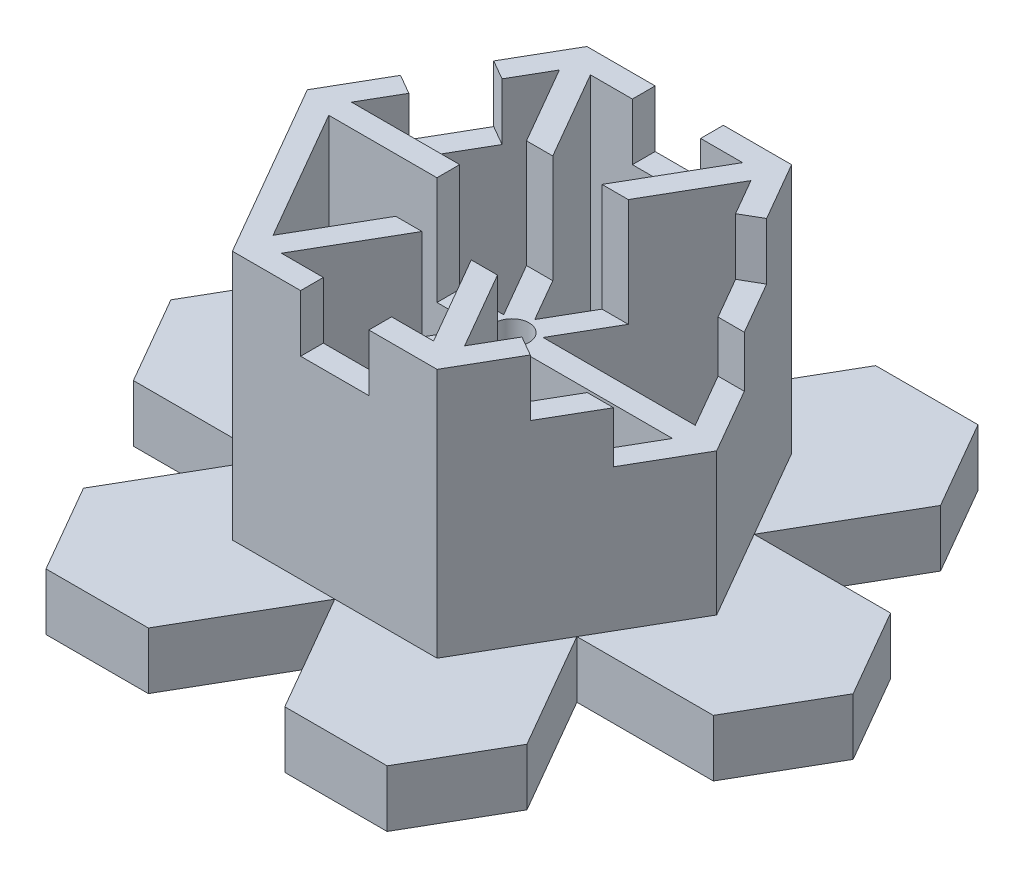
SolidWorks part; units mm, degrees
ref_plane "Alzado" through (0, 0, 0) normal (0, 0, 1) x (1, 0, 0)
ref_plane "Planta" through (0, 0, 0) normal (0, 1, 0) x (1, 0, 0)
ref_plane "Vista lateral" through (0, 0, 0) normal (1, 0, 0) x (0, 0, -1)
sketch "Croquis1" plane through (0, 0, 0) normal (0, 1, 0) x (1, 0, 0)
  line L0 (-30, 51.9615) -> (0, 0) construction
  line L1 (-60, 0) -> (-30, -51.9615) construction
  line L2 (-30, -51.9615) -> (30, -51.9615) construction
  line L3 (30, -51.9615) -> (60, 0) construction
  line L4 (60, 0) -> (30, 51.9615) construction
  line L5 (30, 51.9615) -> (-30, 51.9615) construction
  line L6 (-30, 51.9615) -> (-60, 0) construction
  line L7 (-12, 51.9615) -> (18, 0) construction
  line L8 (18, 0) -> (0, 0) construction
  line L9 (-39, 36.3731) -> (-9, -15.5885) construction
  line L10 (0, 0) -> (-9, -15.5885) construction
  line L11 (39, 36.3731) -> (9, -15.5885) construction
  line L12 (12, 51.9615) -> (-18, 0) construction
  line L13 (51, -15.5885) -> (-9, -15.5885) construction
  line L14 (51, 15.5885) -> (-9, 15.5885) construction
  line L15 (12, -51.9615) -> (-18, 0) construction
  line L16 (39, -36.3731) -> (9, 15.5885) construction
  line L17 (-39, -36.3731) -> (-9, 15.5885) construction
  line L18 (-12, -51.9615) -> (18, 0) construction
  line L19 (-51, 15.5885) -> (9, 15.5885) construction
  line L20 (-51, -15.5885) -> (9, -15.5885) construction
  line L21 (-12, 51.9615) -> (-30, 51.9615)
  line L22 (-30, 51.9615) -> (-39, 36.3731)
  line L23 (-39, 36.3731) -> (-27, 15.5885)
  line L24 (-12, 51.9615) -> (0, 31.1769)
  line L25 (39, 36.3731) -> (30, 51.9615)
  line L26 (30, 51.9615) -> (12, 51.9615)
  line L27 (12, 51.9615) -> (0, 31.1769)
  line L28 (39, 36.3731) -> (27, 15.5885)
  line L29 (51, -15.5885) -> (60, 0)
  line L30 (60, 0) -> (51, 15.5885)
  line L31 (51, 15.5885) -> (27, 15.5885)
  line L32 (51, -15.5885) -> (27, -15.5885)
  line L33 (12, -51.9615) -> (30, -51.9615)
  line L34 (30, -51.9615) -> (39, -36.3731)
  line L35 (39, -36.3731) -> (27, -15.5885)
  line L36 (12, -51.9615) -> (0, -31.1769)
  line L37 (-39, -36.3731) -> (-30, -51.9615)
  line L38 (-30, -51.9615) -> (-12, -51.9615)
  line L39 (-12, -51.9615) -> (0, -31.1769)
  line L40 (-39, -36.3731) -> (-27, -15.5885)
  line L41 (-51, 15.5885) -> (-60, 0)
  line L42 (-60, 0) -> (-51, -15.5885)
  line L43 (-51, -15.5885) -> (-27, -15.5885)
  line L44 (-51, 15.5885) -> (-27, 15.5885)
  circle A0 centre (0, 0) radius 51.9615 construction
  point P1 (-12, 51.9615)
  point P17 (39, 36.3731)
  point P22 (51, -15.5885)
  point P27 (12, -51.9615)
  point P32 (-39, -36.3731)
  point P37 (-51, 15.5885)
  point P42 (0, 0)
  point P70 (0, 0)
  dimension "D1" = 120
  dimension "D2" = 18
  dimension "D3" = 6
  dimension "D4" = 6
extrude "Saliente-Extruir1" add sketch "Croquis1" along normal blind 10
sketch "Croquis2" plane through (0, 10, 0) normal (0, 1, 0) x (1, 0, 0)
  line L0 (2.3094, 0) -> (0, 0) construction
  line L1 (-18, 31.1769) -> (-36, 0)
  line L2 (-36, 0) -> (-18, -31.1769)
  line L3 (-18, -31.1769) -> (18, -31.1769)
  line L4 (18, -31.1769) -> (36, 0)
  line L5 (36, 0) -> (18, 31.1769)
  line L6 (18, 31.1769) -> (-18, 31.1769)
  line L7 (-18, 31.1769) -> (0, 0) construction
  line L8 (-15.6906, 27.1769) -> (-31.3812, 0)
  line L9 (-31.3812, 0) -> (-15.6906, -27.1769)
  line L10 (-15.6906, -27.1769) -> (15.6906, -27.1769)
  line L11 (15.6906, -27.1769) -> (31.3812, 0)
  line L12 (31.3812, 0) -> (15.6906, 27.1769)
  line L13 (15.6906, 27.1769) -> (-15.6906, 27.1769)
  line L14 (-15.6906, 31.1769) -> (2.3094, 0) construction
  line L15 (-19.1547, 29.1769) -> (-1.1547, -2) construction
  line L16 (-1.1547, -2) -> (0, 0) construction
  line L17 (19.1547, 29.1769) -> (1.1547, -2) construction
  line L18 (15.6906, 31.1769) -> (-2.3094, 0) construction
  line L19 (34.8453, -2) -> (-1.1547, -2) construction
  line L20 (34.8453, 2) -> (-1.1547, 2) construction
  line L21 (15.6906, -31.1769) -> (-2.3094, 0) construction
  line L22 (19.1547, -29.1769) -> (1.1547, 2) construction
  line L23 (-19.1547, -29.1769) -> (-1.1547, 2) construction
  line L24 (-15.6906, -31.1769) -> (2.3094, 0) construction
  line L25 (-34.8453, 2) -> (1.1547, 2) construction
  line L26 (-34.8453, -2) -> (1.1547, -2) construction
  line L27 (-15.6906, 27.1769) -> (-16.8453, 25.1769)
  line L28 (-16.8453, 25.1769) -> (-3.4641, 2)
  line L29 (-15.6906, 27.1769) -> (-13.3812, 27.1769)
  line L30 (-13.3812, 27.1769) -> (0, 4)
  line L31 (16.8453, 25.1769) -> (3.4641, 2)
  line L32 (31.3812, 0) -> (15.6906, 27.1769)
  line L33 (15.6906, 27.1769) -> (-15.6906, 27.1769)
  line L34 (13.3812, 27.1769) -> (0, 4)
  line L35 (30.2265, -2) -> (3.4641, -2)
  line L36 (15.6906, -27.1769) -> (31.3812, 0)
  line L37 (31.3812, 0) -> (15.6906, 27.1769)
  line L38 (30.2265, 2) -> (3.4641, 2)
  line L39 (13.3812, -27.1769) -> (0, -4)
  line L40 (-15.6906, -27.1769) -> (15.6906, -27.1769)
  line L41 (15.6906, -27.1769) -> (31.3812, 0)
  line L42 (16.8453, -25.1769) -> (3.4641, -2)
  line L43 (-16.8453, -25.1769) -> (-3.4641, -2)
  line L44 (-31.3812, 0) -> (-15.6906, -27.1769)
  line L45 (-15.6906, -27.1769) -> (15.6906, -27.1769)
  line L46 (-13.3812, -27.1769) -> (0, -4)
  line L47 (-30.2265, 2) -> (-3.4641, 2)
  line L48 (-15.6906, 27.1769) -> (-31.3812, 0)
  line L49 (-31.3812, 0) -> (-15.6906, -27.1769)
  line L50 (-30.2265, -2) -> (-3.4641, -2)
  circle A0 centre (0, 0) radius 31.1769 construction
  circle A1 centre (0, 0) radius 27.1769 construction
  point P43 (0, 0)
  point P83 (0, 0)
  dimension "D1" = 4
  dimension "D2" = 2
  dimension "D3" = 6
  dimension "D4" = 6
extrude "Saliente-Extruir2" add sketch "Croquis2" along normal blind 170 contours L5 L6 L1 L2 L3 L4 L13 L12 L37 L11 L41 L10 L45 L9 L49 L8 L33 | L9 L50 L43 L10 L46 L39 L11 L42 L35 L12 L38 L31 L13 L34 L30 L8 L28 L47
sketch "Croquis3" plane through (0, 0, 31.1769) normal (0, 0, 1) x (1, 0, 0)
  line L0 (-14, 172) -> (-2, 172)
  line L1 (-2, 172) -> (6, 164)
  line L2 (6, 164) -> (6, 44)
  line L3 (-18, 180) -> (18, 180) construction
  line L4 (-18, 180) -> (-18, 10) construction
  line L5 (18, 180) -> (18, 10) construction
  line L6 (-14, 160) -> (-6.9706, 160)
  line L7 (-6.9706, 160) -> (-6, 159.0294)
  line L8 (-6, 159.0294) -> (-6, 44)
  line L9 (-14, 172) -> (-14, 160)
  line L10 (-6, 44) -> (6, 44)
  dimension "D1" = 8
  dimension "D2" = 4
  dimension "D3" = 12
  dimension "D4" = 135
  dimension "D5" = 120
  dimension "D6" = 12
  dimension "D7" = 12
extrude "Cortar-Extruir1" cut sketch "Croquis3" against normal blind 4
pattern_circular "MatrizC1" count 5 every 60 about axis through (0, 0, 0) along (0, 1, 0) of "Cortar-Extruir1"
sketch "Croquis4" plane through (-27, 0, 15.5885) normal (-0.866, 0, 0.5) x (0.5, 0, 0.866)
  line L2 (-18, 180) -> (18, 10) construction
  line L3 (0, 95) -> (0, 172) construction
  line L4 (-18, 180) -> (18, 180) construction
  line L6 (12, 166) -> (-12, 166)
  line L7 (12, 166) -> (12, 178)
  line L8 (12, 178) -> (-12, 178)
  line L9 (-12, 166) -> (-12, 178)
  line L10 (12, 166) -> (-12, 178) construction
  line L11 (12, 178) -> (-12, 166) construction
  line L12 (0, 178) -> (0, 180) construction
  point P6 (0, 172)
  point P7 (0, 172)
  dimension "D1" = 8
  dimension "D2" = 12
  dimension "D3" = 24
extrude "Saliente-Extruir3" add sketch "Croquis4" along normal blind 36
sketch "Croquis5" plane through (-58.1769, 0, 33.5885) normal (-0.866, 0, 0.5) x (0.5, 0, 0.866)
  line L0 (-12, 169) -> (12, 169)
  line L1 (-12, 166) -> (-12, 178) construction
  line L2 (12, 166) -> (12, 178) construction
  line L3 (12, 166) -> (-12, 166) construction
  line L4 (-12, 169) -> (-12, 178)
  line L5 (-12, 166) -> (-12, 178) construction
  line L6 (-12, 178) -> (12, 178)
  line L7 (12, 178) -> (12, 169)
  dimension "D1" = 3
extrude "Cortar-Extruir2" cut sketch "Croquis5" against normal blind 24
chamfer "Chaflán1" distance 36 angle 70 1 edges at (-27, 166, 15.5885) first distance on face at (-42.5885, 166, 24.5885)
sketch "Croquis6" plane through (-6, 0, -10.3923) normal (-0.5, 0, -0.866) x (-0.866, 0, 0.5)
  line L0 (67.1769, 166) -> (31.1769, 67.0908) construction
  line L1 (31.1769, 67.0908) -> (31.1769, 166) construction
  line L2 (31.1769, 67.0908) -> (31.1769, 178) construction
  line L3 (31.1769, 166) -> (58.6635, 166) construction
  line L4 (58.6635, 166) -> (31.1769, 90.4812)
  line L5 (59.6594, 168.7362) -> (23.6594, 69.827) construction
  line L6 (58.6635, 166) -> (67.1769, 166) construction
  line L7 (31.1769, 90.4812) -> (31.1769, 166)
  line L8 (31.1769, 166) -> (58.6635, 166)
  dimension "D1" = 8
extrude "Cortar-Extruir3" cut sketch "Croquis6" against normal blind 24
sketch "Croquis7" plane through (-58.1769, 0, 33.5885) normal (-0.866, 0, 0.5) x (0.5, 0, 0.866)
  line L1 (12, 166) -> (-18, 166)
  line L2 (12, 166) -> (12, 184)
  line L3 (12, 184) -> (-18, 184)
  line L4 (-18, 166) -> (-18, 184)
  circle A0 centre (-3, 175) radius 3
  dimension "D5" = 6
  dimension "D1" = 30
  dimension "D2" = 18
  dimension "D3" = 9
  dimension "D4" = 15
extrude "Saliente-Extruir4" add sketch "Croquis7" against normal blind 3
sketch "Croquis8" plane through (0, 184, 0) normal (0, 1, 0) x (1, 0, 0)
  line L1 (75, -75) -> (-75, -75)
  line L2 (75, -75) -> (75, 75)
  line L3 (75, 75) -> (-75, 75)
  line L4 (-75, -75) -> (-75, 75)
  line L5 (75, -75) -> (-75, 75) construction
  line L6 (75, 75) -> (-75, -75) construction
  point P0 (0, 0)
  dimension "D1" = 150
extrude "Cortar-Extruir4" cut sketch "Croquis8" against normal blind 130
sketch "Croquis9" plane through (0, 54, 0) normal (0, 1, 0) x (1, 0, 0)
  line L0 (53.3, 0) -> (-11.2, 0) construction
  line L1 (53.3, -11.5) -> (-11.2, -11.5)
  line L2 (53.3, -11.5) -> (53.3, 11.5)
  line L3 (53.3, 11.5) -> (-11.2, 11.5)
  line L4 (-11.2, -11.5) -> (-11.2, 11.5)
  line L5 (53.3, -11.5) -> (-11.2, 11.5) construction
  line L6 (53.3, 11.5) -> (-11.2, -11.5) construction
  circle A0 centre (0, 0) radius 2.5 construction
  point P0 (21.05, 0)
  point P7 (0, 0)
  point P10 (0, 0)
  dimension "D4" = 5
  dimension "D1" = 23
  dimension "D2" = 64.5
  dimension "D3" = 11.2
extrude "Cortar-Extruir5" cut sketch "Croquis9" against normal blind 19 contours A0 | L2 L1 L4 L3
sketch "Croquis10" plane through (0, 35, 0) normal (0, 1, 0) x (1, 0, 0)
  circle A0 centre (0, 0) radius 3
  dimension "D1" = 6
extrude "Cortar-Extruir6" cut sketch "Croquis10" against normal blind 8 body kept at (-36, 10, 0)
